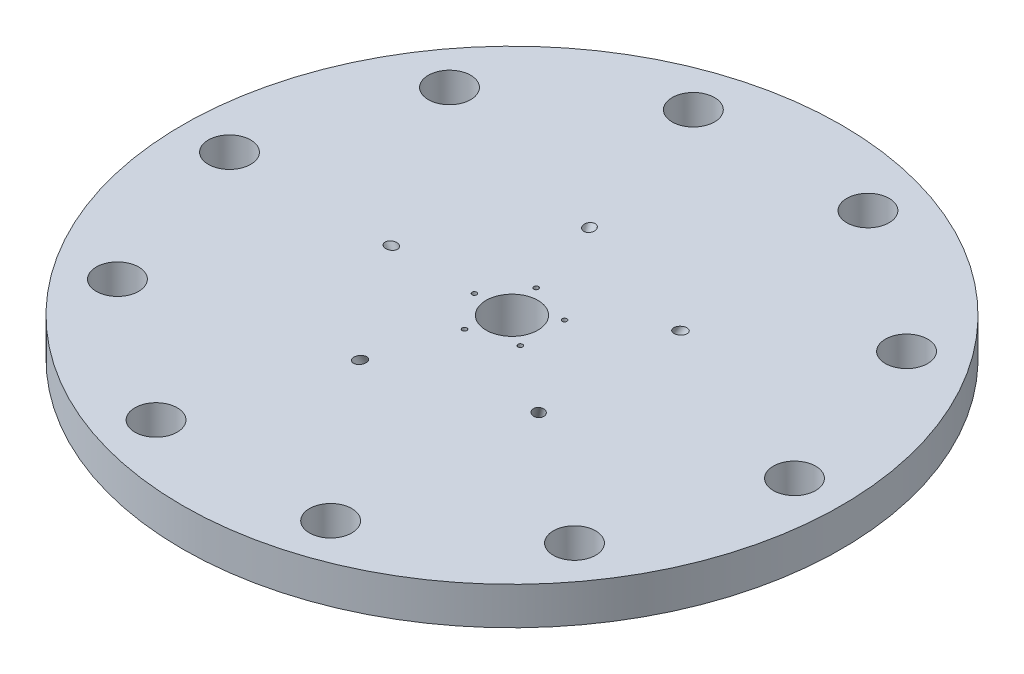
SolidWorks part; units mm, degrees
other "Markup1"
sketch "Sketch22" plane through (67.4, 16.5, 67.4) normal (0.6133, 0.6241, 0.4841) x (0.6587, -0.0661, -0.7495)
sketch "Sketch37" plane through (67.4, 28, 67.4) normal (0.6133, 0.6241, 0.4841) x (0.6587, -0.0661, -0.7495)
other "Markup2"
sketch "Sketch23" plane through (67.4, 26.5, 67.4) normal (0.1362, 0.0894, 0.9866) x (0.9893, -0.0646, -0.1307)
sketch "Sketch38" plane through (67.4, 28, 67.4) normal (0.1362, 0.0894, 0.9866) x (0.9893, -0.0646, -0.1307)
other "Markup5"
sketch "Sketch28" plane through (-67.4, 30.5, 67.4) normal (-0.0176, 0.5562, 0.8308) x (0.9998, 0.0146, 0.0115)
sketch "Sketch39" plane through (-67.4, 28, 67.4) normal (-0.0176, 0.5562, 0.8308) x (0.9998, 0.0146, 0.0115)
material "1023 Carbon Steel Sheet (SS)"
ref_plane "Front Plane" through (0, 0, 0) normal (0, 0, 1) x (1, 0, 0)
ref_plane "Top Plane" through (0, 0, 0) normal (0, 1, 0) x (1, 0, 0)
ref_plane "Right Plane" through (0, 0, 0) normal (1, 0, 0) x (0, 0, -1)
sketch "Sketch1" plane through (0, 0, 0) normal (0, 0, 1) x (1, 0, 0)
  line L5 (-47.4, 0) -> (-47.4, -8)
  line L9 (-7, -8) -> (0, -8)
  line L10 (0, -8) -> (0, 0)
  line L12 (-7, -8) -> (-17.4, -8)
  line L24 (-17.4, -8) -> (-47.4, -8)
  line L25 (-47.4, 0) -> (0, 0)
  dimension "D2" = 8
  dimension "D3" = 47.4
  dimension "D8" = 0
  dimension "D10" = 7
revolve "Revolve1" add sketch "Sketch1" angle 360 about L10
sketch "Sketch4" plane through (0, 0, 0) normal (0, 0, 1) x (1, 0, 0)
  line L0 (0, 0) -> (0, 13.3666) construction
sketch "Sketch2" plane through (0, 0, 0) normal (0, 1, 0) x (1, 0, 0)
  circle A0 centre (-8, 0) radius 0.5
  dimension "D2" = 1
  dimension "D1" = 8
extrude "Fuel holes" cut sketch "Sketch2" against normal up to next from offset 5
pattern_circular "CirPattern1" count 5 over 360 about axis through (0, 0, 0) along (0, 1, 0) of "Fuel holes" reverse direction yes
sketch "Sketch5" plane through (0, 0, 0) normal (1, 0, 0) x (0, 0, -1)
sketch "Sketch19" plane through (0, -8, 0) normal (0, -1, 0) x (1, 0, 0)
  line L0 (-47.4, 0) -> (-70, 0) construction
  circle A1 centre (0, 0) radius 47.4
  circle A2 centre (0, 0) radius 70
  circle A3 centre (-60, 0) radius 4.5
  dimension "D2" = 9
  dimension "D3" = 60
  dimension "D1" = 22.6
extrude "Boss-Extrude2" add sketch "Sketch19" against normal blind 8 contours A1 | A2
extrude "Bolt holes" cut sketch "Sketch19<3>" against normal up to surface (8 mm away) contours A3 up to face at (-1.9721, 0, -7.6085)
sketch "Sketch19<3>" plane through (0, -8, 0) normal (0, -1, 0) x (1, 0, 0) same geometry as "Sketch19"
sketch "Sketch21" plane through (0, 0, 0) normal (0, 0, 1) x (1, 0, 0)
  line L0 (0, 0) -> (51.8972, 0) construction
  line L1 (0, 0) -> (0, -5.4672) construction
sketch "Sketch8" plane through (-29.8564, -8, 0) normal (0, -1, 0) x (-1, 0, 0)
  line L0 (-29.8564, 0) -> (-8.8564, 0) construction
  line L1 (-8.8564, 0) -> (-8.8564, 32.0516) construction
  circle A2 centre (-8.8564, 0) radius 1.75
  dimension "D1" = 3.5
  dimension "D2" = 21
ref_plane "Plane1" through (-21, 0, 0) normal (1, 0, 0) x (0, 0, -1)
ref_plane "Plane2" through (-1.7859, 3.0933, 0) normal (0.5, -0.866, 0) x (0, 0, -1)
sketch "Sketch41" plane through (-1.7859, 3.0933, 0) normal (0.5, -0.866, 0) x (0, 0, -1)
  circle A0 centre (0, -22.1865) radius 1.15
  dimension "D1" = 2.3
extrude "Cut-Extrude7" cut sketch "Sketch41" against normal blind 10 and the other way through all
sketch "Sketch31" plane through (0, -8, 0) normal (0, -1, 0) x (1, 0, 0)
  circle A0 centre (0, 0) radius 27.4
  dimension "D1" = 54.8
sketch "Sketch32" plane through (0, 0, 0) normal (0, 1, 0) x (1, 0, 0)
  circle A0 centre (0, 0) radius 5.5
  dimension "D1" = 11
extrude "Cut-Extrude3" cut sketch "Sketch32" against normal up to next contours A0
sketch "Sketch35" plane through (0, 0, 0) normal (0, 0, 1) x (1, 0, 0)
  line L0 (0, 0) -> (0, 22.3821) construction
pattern_circular "CirPattern9" count 5 over 360 about axis through (0, 0, 0) along (0, 1, 0) of "Cut-Extrude7"
pattern_circular "CirPattern10" count 10 over 360 about axis through (0, 0, 0) along (0, 1, 0) of "Bolt holes"
